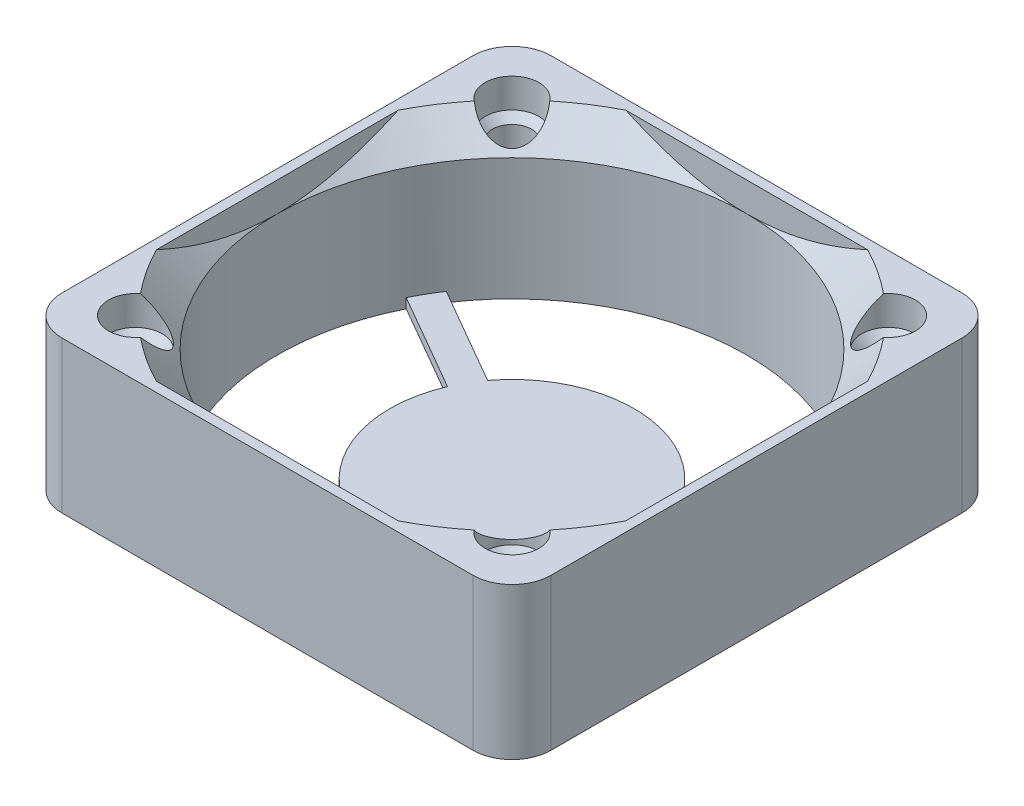
SolidWorks part; units mm, degrees
ref_plane "Front Plane" through (0, 0, 0) normal (0, 0, 1) x (1, 0, 0)
ref_plane "Top Plane" through (0, 0, 0) normal (0, 1, 0) x (1, 0, 0)
ref_plane "Right Plane" through (0, 0, 0) normal (1, 0, 0) x (0, 0, -1)
sketch "Sketch1" plane through (0, 0, 0) normal (0, 1, 0) x (1, 0, 0)
  line L1 (25, 25) -> (-25, 25)
  line L2 (25, 25) -> (25, -25)
  line L3 (25, -25) -> (-25, -25)
  line L4 (-25, 25) -> (-25, -25)
  line L5 (25, 25) -> (-25, -25) construction
  line L6 (25, -25) -> (-25, 25) construction
  circle A0 centre (0, 0) radius 24
  point P0 (0, 0)
  dimension "D3" = 48
  dimension "D1" = 50
  dimension "D2" = 50
extrude "Boss-Extrude1" add sketch "Sketch1" along normal blind 15.5
chamfer "Chamfer1" distance 3 angle 45 1 edges at (0, 15.5, 24)
sketch "Sketch4" plane through (0, 15.5, 0) normal (0, 1, 0) x (1, 0, 0)
  line L0 (-24, 24) -> (-24, -24)
  line L1 (25, 25) -> (-25, 25)
  line L2 (25, 25) -> (25, -25)
  line L3 (25, -25) -> (-25, -25)
  line L4 (-25, 25) -> (-25, -25)
  line L5 (25, 25) -> (-25, -25) construction
  line L6 (25, -25) -> (-25, 25) construction
  line L7 (24, -24) -> (-24, -24)
  line L8 (24, 24) -> (24, -24)
  line L9 (24, 24) -> (-24, 24)
  point P0 (0, 0)
  dimension "D1" = 1
extrude "Boss-Extrude2" add sketch "Sketch4" against normal blind 15.5
sketch "Sketch5" plane through (0, 15.5, 0) normal (0, 1, 0) x (1, 0, 0)
  line L0 (-25, 25) -> (-25, -25) construction
  line L1 (25, 25) -> (-25, 25) construction
  line L2 (-25, -25) -> (25, -25) construction
  line L3 (25, -25) -> (25, 25) construction
  circle A0 centre (-19.25, 19.25) radius 2.75
  circle A1 centre (19.25, 19.25) radius 2.75
  circle A2 centre (19.25, -19.25) radius 2.75
  circle A3 centre (-19.25, -19.25) radius 2.75
  dimension "D2" = 5.5
  dimension "D4" = 5.5
  dimension "D5" = 5.5
  dimension "D6" = 5.5
  dimension "D1" = 5.75
  dimension "D3" = 5.75
  dimension "D7" = 5.75
  dimension "D8" = 5.75
  dimension "D9" = 5.75
  dimension "D10" = 5.75
  dimension "D11" = 5.75
  dimension "D12" = 5.75
extrude "Cut-Extrude1" cut sketch "Sketch5" against normal blind 3
fillet "Fillet1" radius 4 4 edges at (25, 7.75, -25) (25, 7.75, 25) (-25, 7.75, 25) (-25, 7.75, -25)
sketch "Sketch6" plane through (0, 0, 0) normal (0, 1, 0) x (1, 0, 0)
  circle A0 centre (0, 0) radius 12.5
  point P3 (0, -12.5)
  point P8 (12.5, 0)
  dimension "D1" = 25
extrude "Boss-Extrude5" add sketch "Sketch6" along normal blind 1 separate body
sketch "Sketch7" plane through (0, 12.5, 0) normal (0, 1, 0) x (1, 0, 0)
  circle A0 centre (-19.25, 19.25) radius 2
  circle A1 centre (-19.25, -19.25) radius 2
  circle A2 centre (19.25, -19.25) radius 2
  circle A3 centre (19.25, 19.25) radius 2
  dimension "D1" = 4
  dimension "D2" = 4
  dimension "D3" = 4
  dimension "D4" = 4
extrude "Cut-Extrude2" cut sketch "Sketch7" against normal blind 21
chamfer "Chamfer3" distance 0.75 angle 45 4 edges at (-19.25, 12.5, 21.25) (19.25, 12.5, 21.25) (19.25, 12.5, -17.25) (-19.25, 12.5, -17.25)
sketch "Sketch9" plane through (0, 0, 0) normal (0, -1, 0) x (1, 0, 0)
  line L1 (-1.5, 0.5) -> (1.5, 0.5)
  line L2 (-1.5, 0.5) -> (-1.5, 24.5)
  line L3 (-1.5, 24.5) -> (1.5, 24.5)
  line L4 (1.5, 0.5) -> (1.5, 24.5)
  line L5 (-1.5, 0.5) -> (1.5, 24.5) construction
  line L6 (-1.5, 24.5) -> (1.5, 0.5) construction
  circle A0 centre (0, 0) radius 12.5 construction
  point P0 (0, 12.5)
  dimension "D1" = 24
  dimension "D2" = 3
  dimension "D3" = 0
extrude "Boss-Extrude6" add sketch "Sketch9" against normal blind 1
pattern_circular "CirPattern1" count 3 over 360 about axis through (0, 0, 0) along (0, 1, 0) of "Boss-Extrude6"
